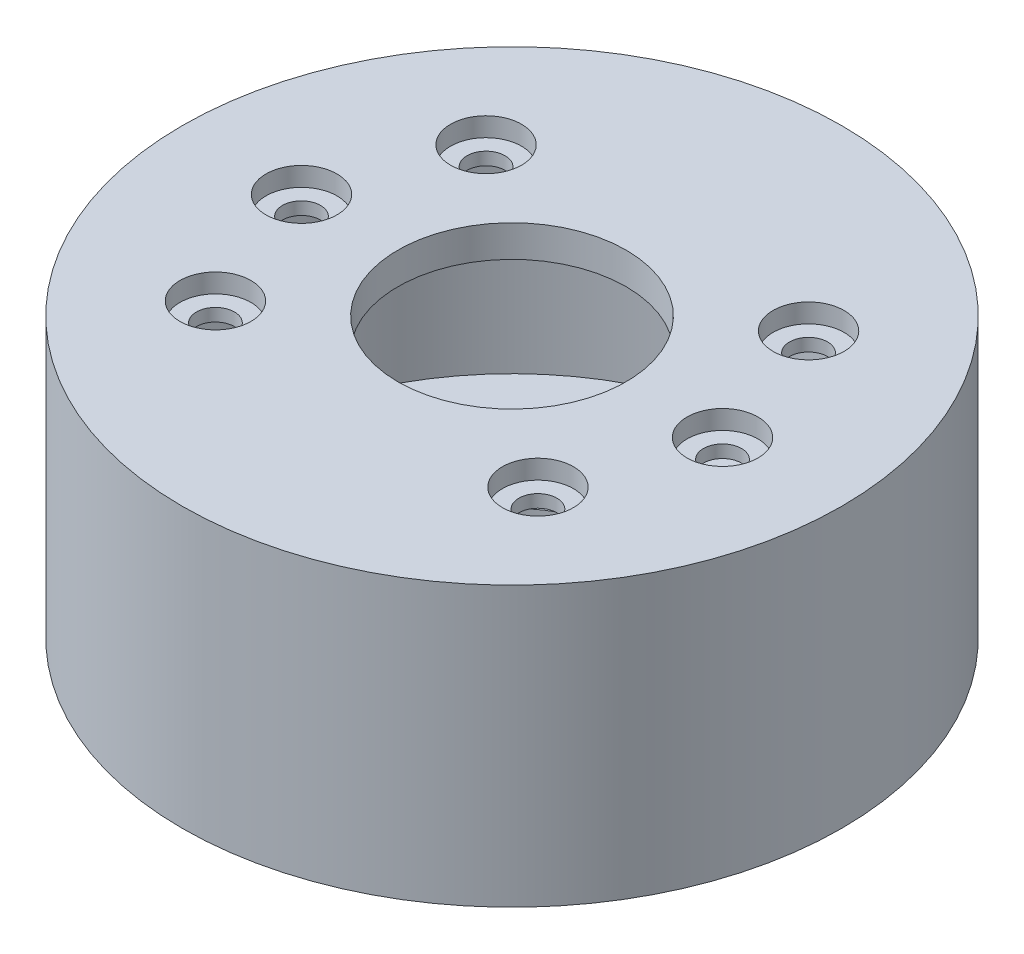
SolidWorks part; units mm, degrees
ref_plane "Front Plane" through (0, 0, 0) normal (0, 0, 1) x (1, 0, 0)
ref_plane "Top Plane" through (0, 0, 0) normal (0, 1, 0) x (1, 0, 0)
ref_plane "Right Plane" through (0, 0, 0) normal (1, 0, 0) x (0, 0, -1)
sketch "Sketch1" plane through (0, 0, 0) normal (0, 1, 0) x (1, 0, 0)
  line L0 (12.7163, 10.6703) -> (0, 0) construction
  line L1 (0, 21.6534) -> (0, -27.8122) construction
  line L2 (-17.8639, 0) -> (22.5422, 0) construction
  line L3 (192.5, 6.25) -> (210, 6.25) construction
  line L5 (175, 12.5) -> (210, 12.5)
  line L6 (175, 12.5) -> (175, 0) construction
  line L7 (175, 0) -> (210, 0)
  line L8 (210, 12.5) -> (210, 0)
  line L9 (175, 12.5) -> (210, 0) construction
  line L10 (175, 0) -> (210, 12.5) construction
  line L12 (192.5, 6.25) -> (175, 6.25) construction
  line L14 (41.8131, 0) -> (75.7048, 15.2376)
  line L15 (41.8131, 0) -> (75.7048, -15.2376)
  line L17 (218.93, 6.25) -> (236.27, 6.25) construction
  line L18 (236.27, 6.25) -> (236.27, 0) construction
  circle A0 centre (0, 0) radius 16.6 construction
  circle A1 centre (16.6, 0) radius 1.5
  circle A2 centre (12.7163, 10.6703) radius 1.5
  circle A3 centre (12.7163, -10.6703) radius 1.5
  circle A4 centre (-12.7163, 10.6703) radius 1.5
  circle A5 centre (-12.7163, -10.6703) radius 1.5
  circle A6 centre (-16.6, 0) radius 1.5
  circle A7 centre (0, 0) radius 9
  circle A8 centre (0, 0) radius 22
  circle A9 centre (183.75, 6.25) radius 2.5
  circle A10 centre (201.25, 6.25) radius 2.5
  circle A11 centre (0, 0) radius 26
  circle A12 centre (236.27, 0) radius 20
  point P21 (192.5, 6.25)
  point P22 (0, 0)
  point P28 (0, 0)
  point P29 (0, 0)
  point P43 (0, 0)
  point P44 (197.6857, 0)
  point P45 (0, 0)
  point P46 (196.6533, -3.194)
  point P47 (194.2713, -4.409)
  point P48 (192.8465, 2.5866)
  point P49 (154.9204, -14.8577)
  point P50 (0, 0)
  point P52 (181.2929, 6.25)
  dimension "D1" = 33.2
  dimension "D2" = 3
  dimension "D3" = 3
  dimension "D5" = 18
  dimension "D6" = 44
  dimension "D8" = 12.5
  dimension "D10" = 5
  dimension "D11" = 5
  dimension "D12" = 52
  dimension "D14" = 17.34
  dimension "D16" = 40
  dimension "D4" = 40
  dimension "D7" = 6.25
  dimension "D9" = 35
  dimension "D13" = 17.68
  dimension "D15" = 6.25
  dimension "D17" = 210
extrude "Boss-Extrude1" add sketch "Sketch1" along normal blind 22 contours A8 L7 L8 L5 A10 A9 region at (-25.2646, 0, 0)
extrude "Boss-Extrude2" add sketch "Sketch1<3>" along normal blind 2.5 contours A8 A6 A5 A3 A2 A1 A4 A7 | A11 A8 | A11 L15 L14 region at (-21.3777, 0, 0) region at (-25.2646, 0, 0)
sketch "Sketch1<3>" plane through (0, 0, 0) normal (0, 1, 0) x (1, 0, 0) same geometry as "Sketch1"
extrude "Boss-Extrude3" add sketch "Sketch1<4>" against normal blind 2.5 from surface contours A8 A6 A5 A3 A2 A1 A4 A7 | A11 A8 | A11 L15 L14 region at (-21.3777, 0, 0) region at (-25.2646, 0, 0) starting at face at (0, 22, 22)
sketch "Sketch1<4>" plane through (0, 0, 0) normal (0, 1, 0) x (1, 0, 0) same geometry as "Sketch1"
fillet "Fillet1" radius 5 rebuild error yes
fillet "Fillet2" radius 5 rebuild error yes
sketch "Sketch2" plane through (0, 0, 0) normal (0, -1, 0) x (1, 0, 0)
  line L0 (0, 0) -> (12.7163, 10.6703) construction
  line L1 (0, 0) -> (16.6, 0) construction
  line L2 (0, 0) -> (-12.7163, 10.6703) construction
  line L3 (0, 0) -> (-16.6, 0) construction
  circle A0 centre (0, 0) radius 16.6 construction
  circle A1 centre (-12.7163, 10.6703) radius 1.5 construction
  circle A2 centre (-16.6, 0) radius 1.5 construction
  circle A3 centre (-12.7163, -10.6703) radius 1.5 construction
  circle A4 centre (12.7163, -10.6703) radius 1.5 construction
  circle A5 centre (16.6, 0) radius 1.5 construction
  circle A6 centre (12.7163, 10.6703) radius 1.5 construction
  circle A7 centre (-12.7163, 10.6703) radius 1.5 construction
  circle A8 centre (-16.6, 0) radius 1.5 construction
  circle A9 centre (-12.7163, -10.6703) radius 1.5 construction
  circle A10 centre (12.7163, -10.6703) radius 1.5 construction
  circle A11 centre (16.6, 0) radius 1.5 construction
  circle A12 centre (12.7163, 10.6703) radius 1.5 construction
  circle A13 centre (12.7163, 10.6703) radius 2.8
  circle A14 centre (16.6, 0) radius 2.8
  circle A15 centre (12.7163, -10.6703) radius 2.8
  circle A16 centre (-12.7163, 10.6703) radius 2.8
  circle A17 centre (-16.6, 0) radius 2.8
  circle A18 centre (-12.7163, -10.6703) radius 2.8
  dimension "D1" = 33.2
  dimension "D2" = 5.6
  dimension "D5" = 5.6
  dimension "D4" = 40
  dimension "D7" = 40
  dimension "D3" = 3
  dimension "D6" = 3
extrude "Cut-Extrude3" cut sketch "Sketch2" against normal blind 1.5
extrude "Cut-Extrude4" cut sketch "Sketch2<3>" along normal blind 1.5 from surface starting at face at (0, 22, 26)
sketch "Sketch2<3>" plane through (0, 0, 0) normal (0, -1, 0) x (1, 0, 0) same geometry as "Sketch2"
fillet "Fillet3" radius 1.5 rebuild error yes tangent propagation no
sketch "Sketch3" plane through (0, 0, 0) normal (0, 0, 1) x (1, 0, 0)
  line L2 (5.1955, -25.1899) -> (29.4878, 12.6899)
  line L5 (-8.1809, -7.9016) -> (-45.0927, -7.9016)
  line L6 (-45.0927, -4.9016) -> (-45.0927, 3.9016)
  line L7 (-45.0927, 7.9016) -> (-5.1592, 7.9016)
  line L10 (6.5451, -23.0855) -> (28.1382, 10.5855)
  circle A2 centre (-17.6768, 0) radius 2.5
  circle A3 centre (-35.1768, 0) radius 2.5
  point P2 (0, 0)
  point P5 (17.3416, -6.25)
  point P19 (17.5626, -5.9054)
  dimension "D1" = 17.3416
  dimension "D2" = 6.25
  dimension "D3" = 17.6768
  dimension "D4" = 32.672
sketch "Sketch4" plane through (0, 0, 0) normal (0, -1, 0) x (1, 0, 0)
  line L0 (201.25, 0) -> (218.9268, 0) construction
  line L1 (218.9268, 0) -> (236.2678, 0) construction
  line L2 (236.2678, 0) -> (236.2678, -6.25) construction
  line L3 (225.4713, -23.0855) -> (247.0644, 10.5855)
  circle A0 centre (201.25, 0) radius 1.1389 construction
  circle A1 centre (236.2678, -6.25) radius 20
  point P9 (236.2678, -6.25)
  point P11 (247.0644, 10.5855)
  dimension "D1" = 17.6768
  dimension "D5" = 40
  dimension "D2" = 17.341
  dimension "D3" = 6.25
  dimension "D4" = 32.672
